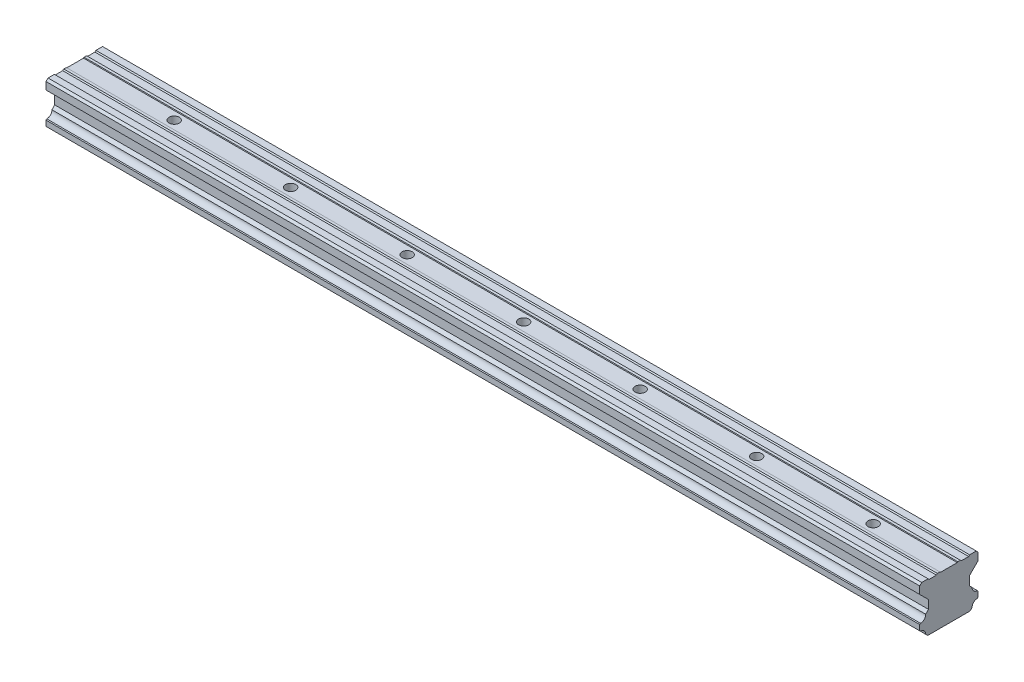
SolidWorks part; units mm, degrees
material "ASTM A36 Steel"
ref_plane "Front Plane" through (0, 0, 0) normal (0, 0, 1) x (1, 0, 0)
ref_plane "Top Plane" through (0, 0, 0) normal (0, 1, 0) x (1, 0, 0)
ref_plane "Right Plane" through (0, 0, 0) normal (1, 0, 0) x (0, 0, -1)
sketch "Sketch1" plane through (0, 0, 0) normal (1, 0, 0) x (0, 0, -1)
  line L0 (-7.9658, -7.694) -> (-7.2663, -8.3935)
  line L1 (-7.2663, -8.3935) -> (7.2663, -8.3935)
  line L2 (7.2663, -8.3935) -> (7.9658, -7.694)
  line L3 (9.7474, -5.9133) -> (10, -5.6608)
  line L4 (10, -5.6608) -> (10, -3.7884)
  line L5 (10, -3.7884) -> (9.7474, -3.5358)
  line L6 (7.9658, -1.7232) -> (7.0051, -0.7626)
  line L7 (7.0051, -0.7626) -> (7.0051, 2.1662)
  line L8 (7.0051, 2.1662) -> (10, 5.1611)
  line L9 (10, 5.1611) -> (10, 7.7124)
  line L10 (10, 7.7124) -> (9.4085, 8.3935)
  line L11 (9.4085, 8.3935) -> (7.133, 8.3935)
  line L12 (7.133, 8.3935) -> (6.7895, 8.05)
  line L13 (6.7895, 8.05) -> (4.2711, 8.05)
  line L14 (4.2711, 8.05) -> (3.9277, 8.3935)
  line L15 (3.9277, 8.3935) -> (3.0613, 8.3935)
  line L16 (3.0613, 8.3935) -> (2.872, 8.2042)
  line L17 (2.872, 8.2042) -> (-2.872, 8.2042)
  line L18 (-2.872, 8.2042) -> (-3.0613, 8.3935)
  line L19 (-3.0613, 8.3935) -> (-3.9277, 8.3935)
  line L20 (-3.9277, 8.3935) -> (-4.2712, 8.05)
  line L21 (-4.2712, 8.05) -> (-6.7895, 8.05)
  line L22 (-6.7895, 8.05) -> (-7.133, 8.3935)
  line L23 (-7.133, 8.3935) -> (-9.3077, 8.3935)
  line L24 (-9.3077, 8.3935) -> (-10, 7.7012)
  line L25 (-10, 7.7012) -> (-10, 5.1611)
  line L26 (-10, 5.1611) -> (-7.0051, 2.1662)
  line L27 (-7.0051, 2.1662) -> (-7.0051, -0.7626)
  line L28 (-7.0051, -0.7626) -> (-7.9658, -1.7232)
  line L29 (-9.7474, -5.9133) -> (-10, -5.6608)
  line L30 (-10, -5.6608) -> (-10, -3.7884)
  line L31 (-10, -3.7884) -> (-9.7474, -3.5358)
  arc A0 (-7.9658, -7.694) -> (-9.7474, -5.9133) centre (-9.7035, -7.6511) ccw
  arc A1 (-9.7474, -3.5358) -> (-7.9658, -1.7232) centre (-9.7025, -1.7981) ccw
  arc A2 (7.9658, -1.7232) -> (9.7474, -3.5358) centre (9.7025, -1.7981) ccw
  arc A3 (9.7474, -5.9133) -> (7.9658, -7.694) centre (9.7035, -7.6511) ccw
extrude "Boss-Extrude1" add sketch "Sketch1" along normal blind 300
sketch "Sketch2" plane through (0, -8.3935, 0) normal (0, -1, 0) x (1, 0, 0)
  circle A0 centre (34, 0) radius 3
  dimension "D1" = 6
  dimension "D2" = 34
hole_wizard "Hole1" positions "3DSketch1" profile "Sketch3" legacy end condition through all
sketch3d "3DSketch1"
  point P0 (34, -8.3935, 0)
sketch "Sketch3" plane through (34, -8.3935, 0) normal (1, 0, 0) x (0, 0, -1)
  line L0 (0, 0) -> (0, 16.7869)
  line L1 (0, 16.7869) -> (1.75, 16.7869)
  line L2 (1.75, 16.7869) -> (1.75, 4.5)
  line L3 (1.75, 4.5) -> (3, 4.5)
  line L4 (3, 4.5) -> (3, 0)
  line L5 (3, 0) -> (0, 0)
  line L6 (0, 110) -> (0, -10) construction
  dimension "Diameter" = 3.5
  dimension "Depth" = 16.7869
  dimension "C-Bore Diameter" = 6
  dimension "C-Bore Depth" = 4.5
sketch "Sketch4" plane through (0, -8.3935, 0) normal (0, -1, 0) x (-1, 0, 0)
  line L0 (0, 0) -> (-300, 0) construction
  line L1 (-300, -7.2663) -> (-300, 7.2663) construction
pattern_linear "LPattern1" count 7 spacing 40 along (1, 0, 0) of "Hole1"
